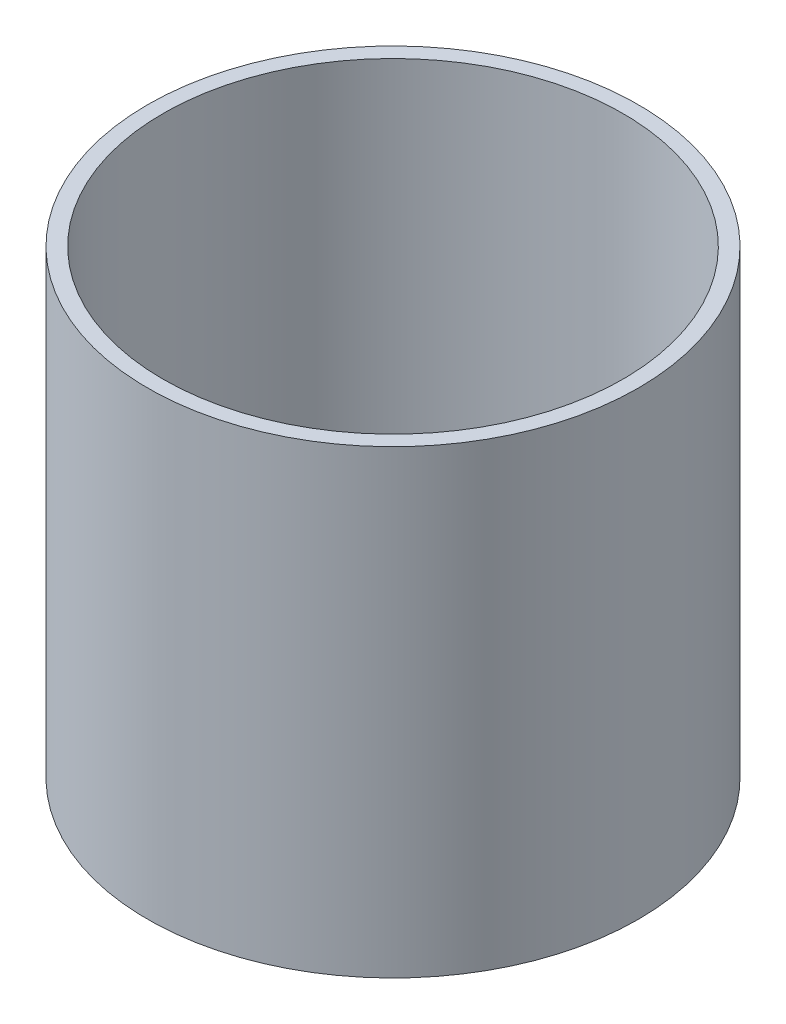
SolidWorks part; units mm, degrees
ref_plane "Front Plane" through (0, 0, 0) normal (0, 0, 1) x (1, 0, 0)
ref_plane "Top Plane" through (0, 0, 0) normal (0, 1, 0) x (1, 0, 0)
ref_plane "Right Plane" through (0, 0, 0) normal (1, 0, 0) x (0, 0, -1)
sketch "Sketch1" plane through (0, 0, 0) normal (0, 1, 0) x (1, 0, 0)
  circle A0 centre (0, 0) radius 30
  dimension "D1" = 60
extrude "Extrude-Thin1" add sketch "Sketch1" along normal blind 60 thin thin type one direction wall 2
